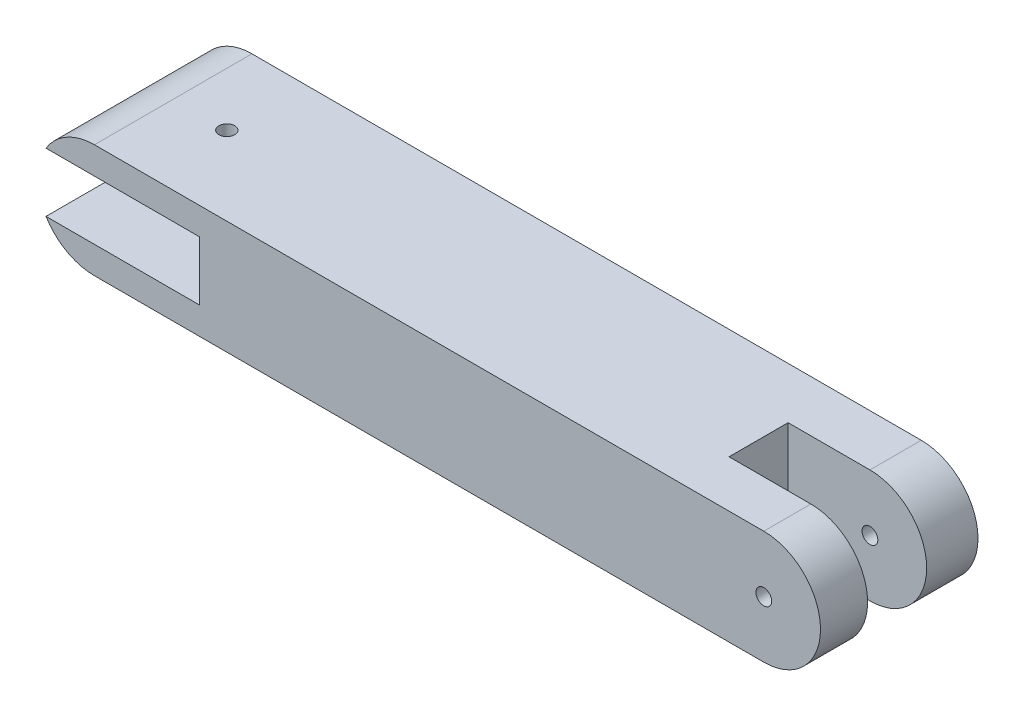
SolidWorks part; units mm, degrees
ref_plane "Plano frontal" through (0, 0, 0) normal (0, 0, 1) x (1, 0, 0)
ref_plane "Plano superior" through (0, 0, 0) normal (0, 1, 0) x (1, 0, 0)
ref_plane "Plano direito" through (0, 0, 0) normal (1, 0, 0) x (0, 0, -1)
sketch "Esboço1" plane through (0, 0, 0) normal (0, 0, 1) x (1, 0, 0)
  line L0 (-60.6729, 0) -> (-76.5569, 0) construction
  line L2 (-76.5569, 14.4058) -> (93.4431, 14.4058)
  line L4 (-76.5569, -14.4058) -> (93.4431, -14.4058)
  arc A0 (93.4431, 14.4058) -> (93.4431, -14.4058) centre (93.4431, 0) cw
  arc A1 (-76.5569, -14.4058) -> (-76.5569, 14.4058) centre (-76.5569, 0) cw
  point P0 (0, 0)
  point P4 (0, 0)
extrude "Ressalto-extrusão1" add sketch "Esboço1" along normal blind 40
sketch "Esboço2" plane through (0, 0, 40) normal (0, 0, 1) x (1, 0, 0)
  circle A0 centre (93.4431, 0) radius 2
extrude "Corte-extrusão1" cut sketch "Esboço2" against normal mid plane 80
sketch "Esboço3" plane through (0, 0, 40) normal (0, 0, 1) x (1, 0, 0)
  line L0 (-50.1206, 0) -> (-106.7517, 0) construction
  line L6 (-49.8464, 7.5) -> (-92.4422, 7.5)
  line L7 (-49.8464, 7.5) -> (-49.8464, -7.5)
  line L8 (-49.8464, -7.5) -> (-92.4422, -7.5)
  line L9 (-92.4422, 7.5) -> (-92.4422, -7.5)
  line L10 (-49.8464, 7.5) -> (-92.4422, -7.5) construction
  line L11 (-49.8464, -7.5) -> (-92.4422, 7.5) construction
  point P0 (-50.1206, 0)
  point P3 (-71.1443, 0)
extrude "Corte-extrusão2" cut sketch "Esboço3" against normal mid plane 80
sketch "Esboço4" plane through (0, 14.4058, 0) normal (0, 1, 0) x (1, 0, 0)
  circle A0 centre (-62.9423, -20) radius 2
extrude "Corte-extrusão3" cut sketch "Esboço4" against normal mid plane 80
sketch "Esboço6" plane through (0, 14.4058, 0) normal (0, 1, 0) x (1, 0, 0)
  line L1 (72.663, -13.0405) -> (114.2314, -13.0405)
  line L2 (72.663, -13.0405) -> (72.663, -28.0405)
  line L3 (72.663, -28.0405) -> (114.2314, -28.0405)
  line L4 (114.2314, -13.0405) -> (114.2314, -28.0405)
  point P0 (0, -20.5405)
extrude "Corte-extrusão5" cut sketch "Esboço6" against normal mid plane 125
